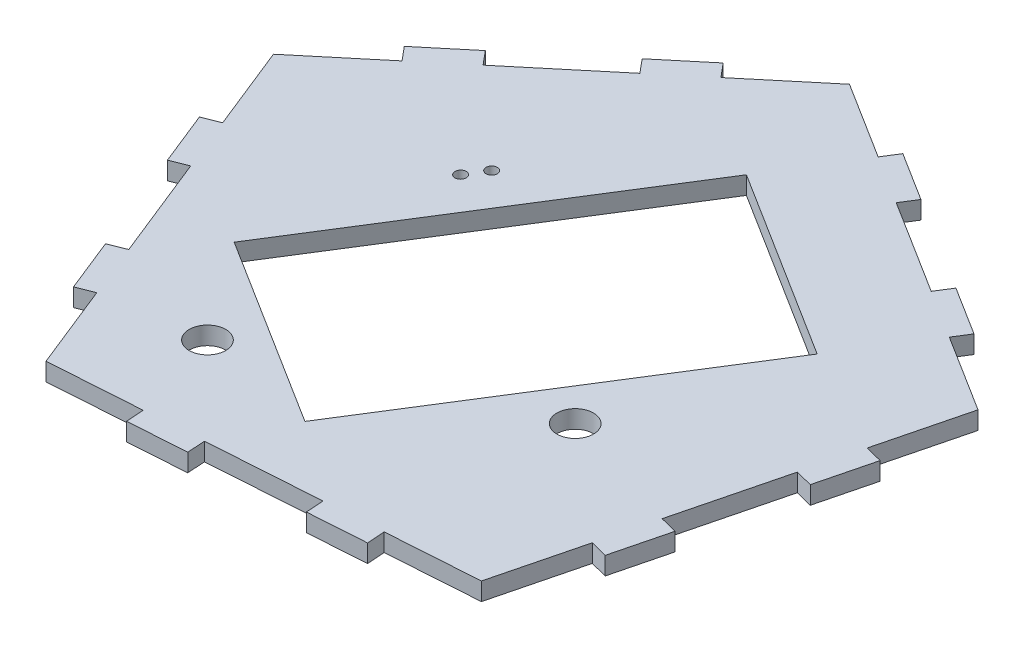
SolidWorks part; units mm, degrees
ref_plane "Front Plane" through (0, 0, 0) normal (0, 0, 1) x (1, 0, 0)
ref_plane "Top Plane" through (0, 0, 0) normal (0, 1, 0) x (1, 0, 0)
ref_plane "Right Plane" through (0, 0, 0) normal (1, 0, 0) x (0, 0, -1)
sketch "Sketch1" plane through (0, 0, 0) normal (0, 1, 0) x (1, 0, 0)
  line L1 (-59.9258, 15.1181) -> (-32.8962, -52.3211)
  line L2 (-32.8962, -52.3211) -> (39.5948, -47.4543)
  line L3 (39.5948, -47.4543) -> (57.3672, 22.9927)
  line L4 (57.3672, 22.9927) -> (-4.14, 61.6646)
  line L5 (-4.14, 61.6646) -> (-59.9258, 15.1181)
  circle A0 centre (0, 0) radius 50 construction
  dimension "D1" = 100
extrude "Boss-Extrude1" add sketch "Sketch1" along normal blind 3.18
ref_axis "Axis" through (0, 3.339, 0) along (0, -1, 0)
sketch "Axis Check" plane through (0, 3.18, 0) normal (0, 1, 0) x (1, 0, 0)
  line L0 (3.3493, -49.8877) -> (-4.14, 61.6646) construction
  line L1 (-32.8962, -52.3211) -> (39.5948, -47.4543) construction
  line L2 (57.3672, 22.9927) -> (-46.411, -18.6015) construction
  line L3 (-59.9258, 15.1181) -> (-32.8962, -52.3211) construction
  line L4 (-32.0329, 38.3913) -> (39.5948, -47.4543) construction
  line L5 (-4.14, 61.6646) -> (-59.9258, 15.1181) construction
  line L6 (-59.9258, 15.1181) -> (48.481, -12.2308) construction
  line L7 (39.5948, -47.4543) -> (57.3672, 22.9927) construction
  line L8 (-32.8962, -52.3211) -> (26.6136, 42.3287) construction
  line L9 (57.3672, 22.9927) -> (-4.14, 61.6646) construction
sketch "Sketch2" plane through (0, 0, 0) normal (0, -1, 0) x (1, 0, 0)
  line L0 (-53.8107, 0.1392) -> (-50.859, -1.0438)
  line L1 (-53.8107, 0.1392) -> (-50.1723, 9.2172)
  line L2 (-50.859, -1.0438) -> (-47.2205, 8.0342)
  line L3 (-50.1723, 9.2172) -> (-47.2205, 8.0342)
  line L4 (-59.9258, -15.1181) -> (-32.8962, 52.3211) construction
  line L5 (-42.6498, 27.9858) -> (-39.0113, 37.0638)
  line L6 (-42.6498, 27.9858) -> (-39.6981, 26.8028)
  line L7 (-39.0113, 37.0638) -> (-36.0596, 35.8808)
  line L8 (-39.6981, 26.8028) -> (-36.0596, 35.8808)
  line L9 (-46.411, 18.6015) -> (-19.2439, 7.7129) construction
  line L10 (-40.8306, 32.5248) -> (-37.8788, 31.3418) construction
  dimension "D1" = 3.18
  dimension "D2" = 9.78
  dimension "D3" = 10.11
extrude "Cut F" [suppressed] cut sketch "Sketch2" against normal through all
sketch "Sketch4" plane through (0, 3.18, 0) normal (0, 1, 0) x (1, 0, 0)
  line L9 (26.6136, 42.3287) -> (-26.6136, -42.3287) construction
  line L10 (57.3672, 22.9927) -> (-4.14, 61.6646) construction
  line L11 (-34.4964, -17.2915) -> (0.6335, 38.5824)
  line L12 (-34.4964, -17.2915) -> (-0.6335, -38.5824)
  line L13 (0.6335, 38.5824) -> (34.4964, 17.2915)
  line L14 (-0.6335, -38.5824) -> (34.4964, 17.2915)
  line L15 (-34.4964, -17.2915) -> (34.4964, 17.2915) construction
  line L16 (0.6335, 38.5824) -> (-0.6335, -38.5824) construction
  line L20 (0, 0) -> (39.0006, -24.5211) construction
  circle A0 centre (-21.8232, -34.7095) radius 3.25
  circle A1 centre (23.7041, -14.9036) radius 3.25
  point P5 (0, 0)
  point P6 (-21.8232, -34.7095)
  dimension "D3" = 6.5
  dimension "D1" = 40
  dimension "D2" = 66
  dimension "D4" = 8
  dimension "D5" = 8
extrude "Top Cut" cut sketch "Sketch4" against normal blind 10
sketch "Sketch7" plane through (0, 3.18, 0) normal (0, 1, 0) x (1, 0, 0)
  line L0 (0, 0) -> (26.6136, 42.3287) construction
  line L1 (57.3672, 22.9927) -> (-4.14, 61.6646) construction
  line L2 (1.0645, 1.6931) -> (-22.6395, 16.5968) construction
  line L3 (-6.1086, 1.4782) -> (-24.7686, 13.2105) construction
  line L5 (0.6335, 38.5824) -> (-34.4964, -17.2915) construction
  circle A0 centre (-22.6395, 16.5968) radius 1
  circle A1 centre (-24.7686, 13.2105) radius 1
  dimension "D5" = 2
  dimension "D1" = 4
  dimension "D2" = 2
  dimension "D3" = 8
  dimension "D4" = 8
extrude "Top Cut 2" cut sketch "Sketch7" against normal through all
sketch "Sketch8" [suppressed] plane through (0, 3.18, 0) normal (0, 1, 0) x (1, 0, 0)
  line L0 (3.3493, -49.8877) -> (-4.14, 61.6646) construction
  line L5 (-32.8962, -52.3211) -> (39.5948, -47.4543) construction
  line L6 (-17.9455, -31.2723) -> (21.9647, -28.5929)
  line L11 (-17.9455, -31.2723) -> (-21.9647, 28.5929)
  line L12 (21.9647, -28.5929) -> (17.9455, 31.2723)
  line L13 (-21.9647, 28.5929) -> (17.9455, 31.2723)
  point P4 (1.4955, -22.2759)
  dimension "D1" = 60
  dimension "D2" = 40
  dimension "D3" = 20
extrude "Bottom Cut" [suppressed] cut sketch "Sketch8" against normal blind 10
sketch "Sketch9" [suppressed] plane through (0, 3.18, 0) normal (0, 1, 0) x (1, 0, 0)
  line L0 (19.9551, 1.3397) -> (-19.9551, -1.3397) construction
  line L1 (21.9647, -28.5929) -> (17.9455, 31.2723) construction
  line L2 (-21.9647, 28.5929) -> (-17.9455, -31.2723) construction
  line L3 (-19.9551, -1.3397) -> (-44.4689, -2.9855) construction
  line L4 (19.9551, 1.3397) -> (42.6839, 2.8657) construction
  line L5 (-32.8962, -52.3211) -> (39.5948, -47.4543) construction
  line L6 (-29.6051, -6.8886) -> (-32.3788, -7.0748)
  line L7 (-29.6051, -6.8886) -> (-30.2602, 2.8694)
  line L8 (-30.2602, 2.8694) -> (-33.0339, 2.6832)
  line L9 (-32.3788, -7.0748) -> (-33.0339, 2.6832)
  line L10 (-29.6051, -6.8886) -> (-33.0339, 2.6832) construction
  line L11 (-30.2602, 2.8694) -> (-32.3788, -7.0748) construction
  line L12 (33.0339, -2.6832) -> (30.2602, -2.8694)
  line L13 (33.0339, -2.6832) -> (32.3788, 7.0748)
  line L14 (32.3788, 7.0748) -> (29.6051, 6.8886)
  line L15 (30.2602, -2.8694) -> (29.6051, 6.8886)
  line L16 (33.0339, -2.6832) -> (29.6051, 6.8886) construction
  line L17 (32.3788, 7.0748) -> (30.2602, -2.8694) construction
  line L18 (-32.8962, -52.3211) -> (39.5948, -47.4543) construction
  point P6 (-31.3195, -2.1027)
  point P13 (31.3195, 2.1027)
  dimension "D1" = 9.78
  dimension "D4" = 9.78
  dimension "D5" = 10
  dimension "D6" = 10
  dimension "D2" = 2.78
  dimension "D3" = 2.78
extrude "Battery Holder Cut" [suppressed] cut sketch "Sketch9" against normal blind 3.18
sketch "Sketch3" plane through (0, 3.18, 0) normal (0, 1, 0) x (1, 0, 0)
  line L0 (0, 0) -> (-40.9819, 49.1167) construction
  line L1 (-49.5112, 27.9494) -> (-45.4366, 23.066)
  line L3 (-45.4366, 23.066) -> (-37.5894, 29.6135)
  line L4 (-41.664, 34.4969) -> (-37.5894, 29.6135)
  line L5 (-4.14, 61.6646) -> (-59.9258, 15.1181) construction
  line L6 (-71.9961, 5.0469) -> (-69.9588, 2.6052)
  line L7 (-71.9961, 5.0469) -> (-47.4739, 25.5077)
  line L14 (-26.4764, 47.1691) -> (-22.4018, 42.2857)
  line L16 (-22.4018, 42.2857) -> (-14.5546, 48.8333)
  line L17 (-18.6292, 53.7166) -> (-14.5546, 48.8333)
  line L18 (-42.539, 27.5695) -> (-41.513, 26.3398) construction
  line L19 (-49.5112, 27.9494) -> (-41.664, 34.4969)
  line L21 (-26.4764, 47.1691) -> (-18.6292, 53.7166)
  line L22 (-16.5919, 51.275) -> (4.7866, 69.1127)
  line L23 (-39.6267, 32.0552) -> (-24.4391, 44.7274)
  line M18 (-4.14, 61.6646) -> (-59.9258, 15.1181)
  dimension "D1" = 3.18
  dimension "D2" = 10.22
  dimension "D3" = 9.89
  dimension "D4" = 100
extrude "Extrude M" add sketch "Sketch3" against normal up to surface (3.18 mm away) contours L21 L14 L7 L17 | L19 L1 L4 M18 region at (-44.5689, 3.18, -30.0023) region at (-21.5341, 3.18, -49.222) up to face at (-22.6395, 0, -15.5968)
pattern_circular "Circle F" [suppressed] count 5 over 360 about axis through (0, 3.339, 0) along (0, -1, 0) of bodies 173
pattern_circular "Circle M" count 5 over 360 about axis through (0, 3.339, 0) along (0, -1, 0) of "Extrude M"
pattern_circular "Circle Side F" [suppressed] count 5 over 360 about axis through (0, 3.339, 0) along (0, -1, 0) of bodies 173
pattern_circular "Circle Side M" [suppressed] count 5 over 360 about axis through (0, 3.339, 0) along (0, -1, 0) of bodies 168
equation "\"kerf\"= .22mm"
equation "\"tabWidthF\"= 10 - \"kerf\""
equation "\"tabThickness\"= 3.18"
equation "\"D1@Sketch2\"=\"tabThickness\""
equation "\"tabWidthM\"= 10 + \"kerf\""
equation "\"halfkerf\"= \"kerf\" / 2.00mm"
equation "\"D1@Sketch9\"=\"tabWidthF\""
equation "\"D4@Sketch9\"=\"tabWidthF\""
equation "\"D1@Battery Holder Cut\" = \"tabThickness\""
equation "\"tabLength\" = \"kerf\" + 12"
